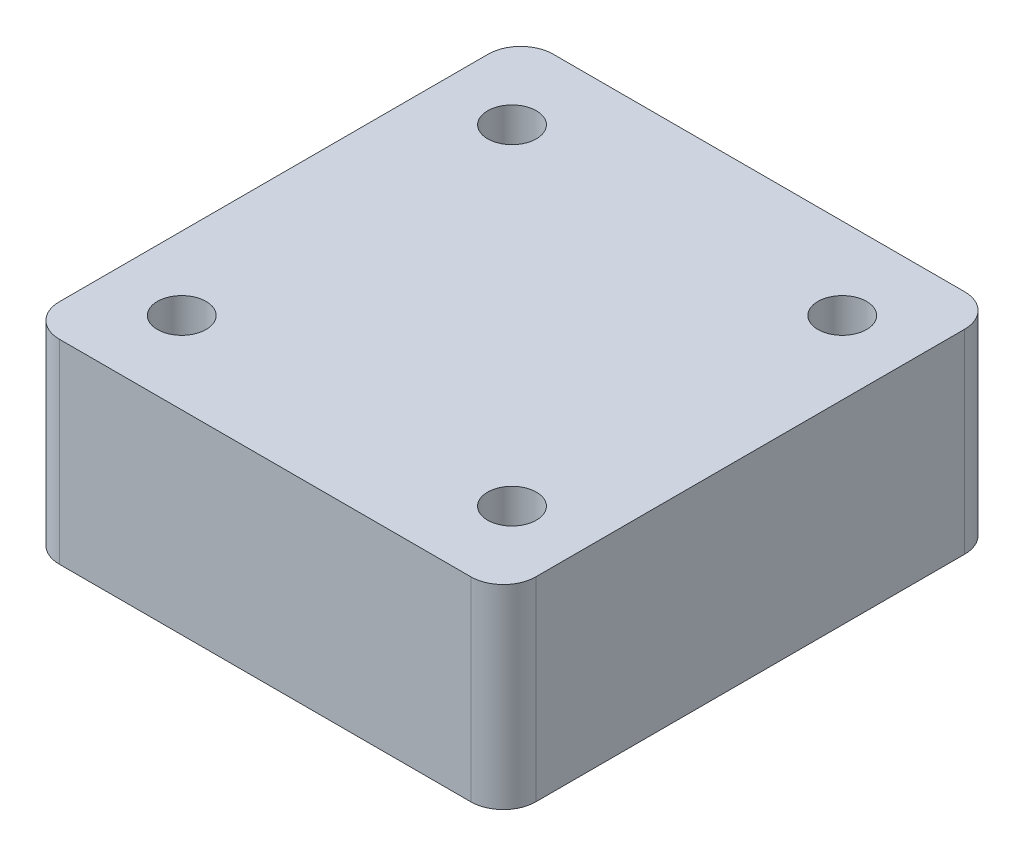
SolidWorks part; units mm, degrees
ref_plane "Front Plane" through (0, 0, 0) normal (0, 0, 1) x (1, 0, 0)
ref_plane "Top Plane" through (0, 0, 0) normal (0, 1, 0) x (1, 0, 0)
ref_plane "Right Plane" through (0, 0, 0) normal (1, 0, 0) x (0, 0, -1)
sketch "Sketch1" plane through (0, 0, 0) normal (0, 1, 0) x (1, 0, 0)
  line L1 (-22, 22.8) -> (22, 22.8)
  line L2 (-22, 22.8) -> (-22, -22.8)
  line L3 (-22, -22.8) -> (22, -22.8)
  line L4 (22, 22.8) -> (22, -22.8)
  line L5 (-22, 22.8) -> (22, -22.8) construction
  line L6 (-22, -22.8) -> (22, 22.8) construction
  point P0 (0, 0)
  dimension "D1" = 44
  dimension "D2" = 45.6
extrude "Boss-Extrude1" add sketch "Sketch1" along normal blind 18
fillet "Fillet1" radius 3 4 edges at (-22, 9, -22.8) (22, 9, -22.8) (22, 9, 22.8) (-22, 9, 22.8)
hole_wizard "M4 Clearance Hole1" positions "Sketch2" profile "Sketch3" hole size "M4" standard "ANSI Metric" end condition through all
sketch "Sketch2" plane through (0, 18, 0) normal (0, 1, 0) x (1, 0, 0)
  line L1 (-15.25, 15.25) -> (15.25, 15.25) construction
  line L2 (-15.25, 15.25) -> (-15.25, -15.25) construction
  line L3 (-15.25, -15.25) -> (15.25, -15.25) construction
  line L4 (15.25, 15.25) -> (15.25, -15.25) construction
  line L5 (-15.25, 15.25) -> (15.25, -15.25) construction
  line L6 (-15.25, -15.25) -> (15.25, 15.25) construction
  point P2 (15.25, -15.25)
  point P35 (-15.25, 15.25)
  point P36 (-15.25, -15.25)
  point P37 (15.25, 15.25)
  point P49 (0, 0)
  dimension "D1" = 30.5
sketch "Sketch3" plane through (15.25, 18, 15.25) normal (1, 0, 0) x (0, 0, 1)
  line L0 (0, 0) -> (0, 18)
  line L1 (0, 18) -> (2.25, 18)
  line L2 (2.25, 18) -> (2.25, 0)
  line L5 (2.25, 0) -> (0, 0)
  line L11 (0, -6.35) -> (0, 107.95) construction
  dimension "Thru Hole Dia." = 4.5
  dimension "Thru Hole Depth" = 18
